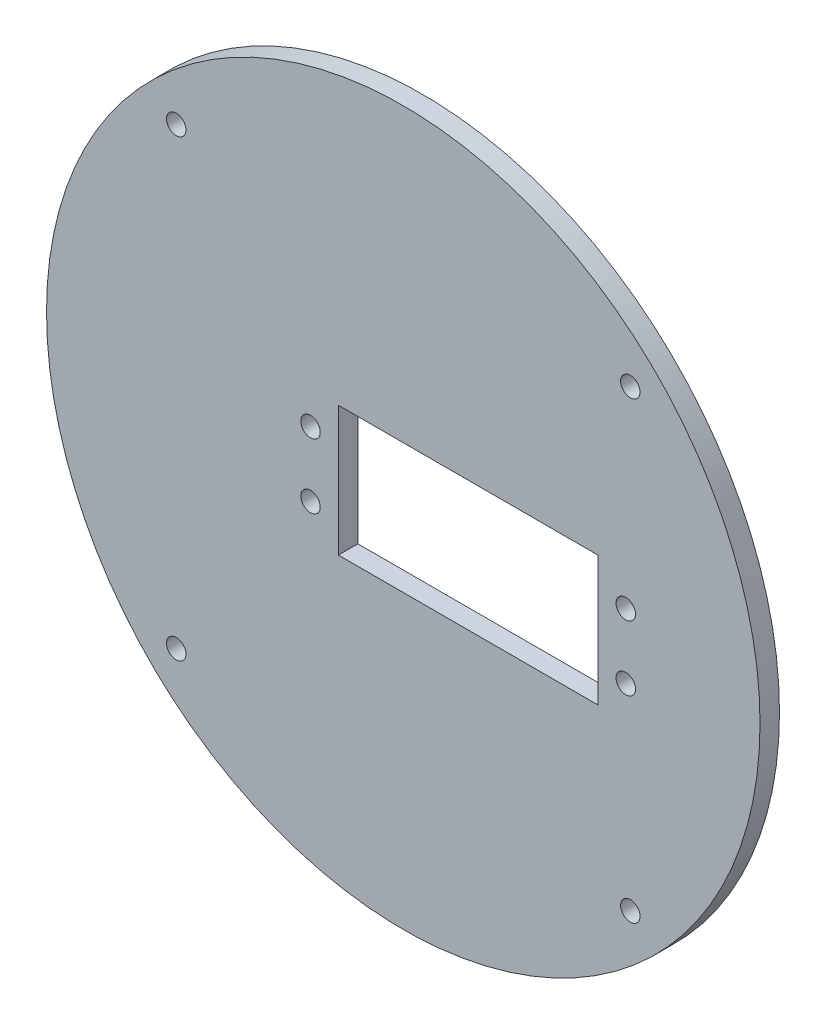
SolidWorks part; units mm, degrees
ref_plane "前视基准面" through (0, 0, 0) normal (0, 0, 1) x (1, 0, 0)
ref_plane "上视基准面" through (0, 0, 0) normal (0, 1, 0) x (1, 0, 0)
ref_plane "右视基准面" through (0, 0, 0) normal (1, 0, 0) x (0, 0, -1)
sketch "草图1" plane through (0, 0, 0) normal (0, 0, 1) x (1, 0, 0)
  line L0 (-35.0018, -35.0018) -> (35.0018, -35.0018)
  line L1 (-35.0018, -35.0018) -> (-35.0018, 35.0018)
  line L2 (-35.0018, 35.0018) -> (35.0018, 35.0018)
  line L3 (35.0018, -35.0018) -> (35.0018, 35.0018)
  line L4 (-35.0018, -35.0018) -> (35.0018, 35.0018) construction
  line L5 (-35.0018, 35.0018) -> (35.0018, -35.0018) construction
  line L7 (-10, 10) -> (30, 10)
  line L8 (-10, 10) -> (-10, -10)
  line L9 (-10, -10) -> (30, -10)
  line L10 (30, 10) -> (30, -10)
  line L11 (-14.3, 5) -> (34.3, 5)
  line L12 (-14.3, 5) -> (-14.3, -5)
  line L13 (-14.3, -5) -> (34.3, -5)
  line L14 (34.3, 5) -> (34.3, -5)
  circle A0 centre (0, 0) radius 55
  circle A1 centre (0, 0) radius 45
  circle A2 centre (-35.0018, 35.0018) radius 1.5
  circle A3 centre (35.0018, 35.0018) radius 1.5
  circle A4 centre (35.0018, -35.0018) radius 1.5
  circle A5 centre (-35.0018, -35.0018) radius 1.5
  circle A6 centre (-14.3, 5) radius 1.5
  circle A7 centre (-14.3, -5) radius 1.5
  circle A8 centre (34.3, 5) radius 1.5
  circle A9 centre (34.3, -5) radius 1.5
  point P16 (-10, 0)
  point P21 (-14.3, 0)
  point P22 (10, 5)
  point P23 (10, 10)
  dimension "D1" = 90
  dimension "D3" = 3
  dimension "D4" = 3
  dimension "D5" = 3
  dimension "D6" = 3
  dimension "D7" = 110
  dimension "D14" = 3
  dimension "D15" = 3
  dimension "D16" = 3
  dimension "D17" = 3
  dimension "D2" = 99
  dimension "D9" = 40
  dimension "D10" = 20
  dimension "D11" = 10
  dimension "D12" = 4.3
  dimension "D13" = 10
extrude "凸台-拉伸2" add sketch "草图1" along normal blind 3 contours A0 A5 L1 A1 A2 L2 A3 L3 A4 L0 | L1 A1 | A9 L13 L10 L9 L8 A7 L12 A6 L11 L7 A8 L3 A1 L2 L1 L0 | L2 A1 | A3 L2 A1 L3 | A9 L3 A1 A8 | L0 A1 | A5 L0 A1 L1 | A7 L13 L8 L11 A6 L12 | A2 L1 A1 L2 | A4 L3 A1 L0 | A9 L14 A8 L11 L10 L13 | A9 L3 A8 L14 region at (-32.7015, -32.7015, 0) region at (-31.1198, -31.1198, 0) region at (0, -39.0418, 0) region at (-39.0418, 0, 0) region at (32.7015, -32.7015, 0) region at (-32.7015, 32.7015, 0) region at (39.071, 0, 0) region at (0, 39.0418, 0) region at (32.7015, 32.7015, 0) region at (34.6537, 0, 0) region at (32.0145, 0, 0) region at (-12.0145, 0, 0) region at (-53.4444, 0, 0)
